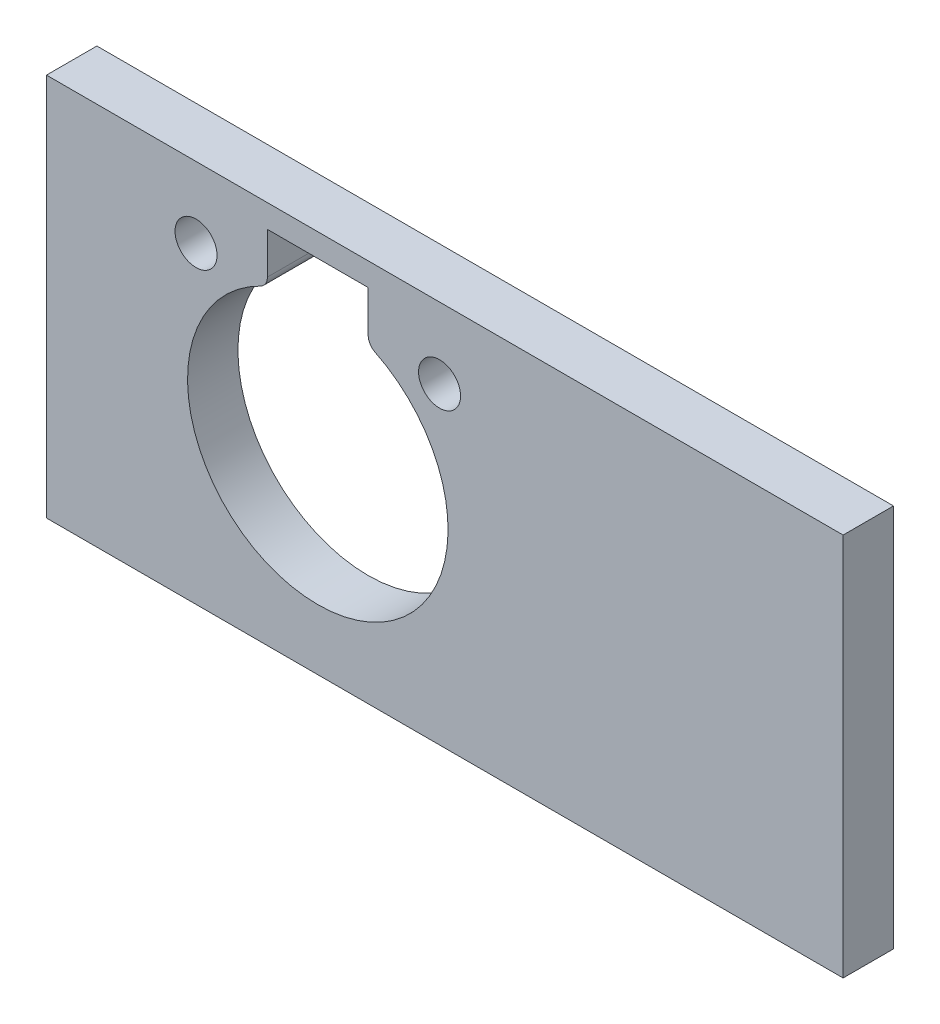
SolidWorks part; units mm, degrees
material "Acrylic (Medium-high impact)"
ref_plane "Front Plane" through (0, 0, 0) normal (0, 0, 1) x (1, 0, 0)
ref_plane "Top Plane" through (0, 0, 0) normal (0, 1, 0) x (1, 0, 0)
ref_plane "Right Plane" through (0, 0, 0) normal (1, 0, 0) x (0, 0, -1)
sketch "Sketch1" plane through (0, 0, 0) normal (0, 0, 1) x (1, 0, 0)
  line L1 (24.6048, 16.0473) -> (-22.8242, 16.0473)
  line L2 (24.6048, 16.0473) -> (24.6048, -6.7927)
  line L3 (24.6048, -6.7927) -> (-22.8242, -6.7927)
  line L4 (-22.8242, 16.0473) -> (-22.8242, -6.7927)
  dimension "D2" = 22.84
extrude "Boss-Extrude1" add sketch "Sketch1" along normal blind 3
sketch "Sketch2" plane through (0, 0, 0) normal (0, 0, -1) x (-1, 0, 0)
  line L9 (3.6718, 14.6698) -> (9.6708, 14.6698)
  line L11 (3.6718, 14.6698) -> (3.6718, 12.2087)
  line L12 (9.6708, 12.2087) -> (9.6708, 14.6698)
  line L13 (3.6718, 14.6698) -> (3.6718, 12.2087)
  line L14 (9.6708, 12.2087) -> (9.6708, 14.6698)
  circle A26 centre (-0.5787, 11.8248) radius 1.25
  circle A27 centre (13.9213, 11.8248) radius 1.25
  arc A29 (9.6708, 12.2087) -> (10.0901, 11.5355) centre (10.4208, 12.2087) ccw
  arc A30 (3.2524, 11.5355) -> (3.6718, 12.2087) centre (2.9218, 12.2087) ccw
  arc A31 (3.2524, 11.5355) -> (10.0901, 11.5355) centre (6.6713, 4.5748) ccw
  arc A32 (9.6708, 12.2087) -> (10.0901, 11.5355) centre (10.4208, 12.2087) ccw
  arc A33 (3.2524, 11.5355) -> (3.6718, 12.2087) centre (2.9218, 12.2087) ccw
  arc A34 (3.2524, 11.5355) -> (10.0901, 11.5355) centre (6.6713, 4.5748) ccw
  dimension "D1" = 0.25
extrude "Cut-Extrude1" cut sketch "Sketch2" against normal up to surface (3 mm away) up to face at (0.8903, 4.6273, 3)
